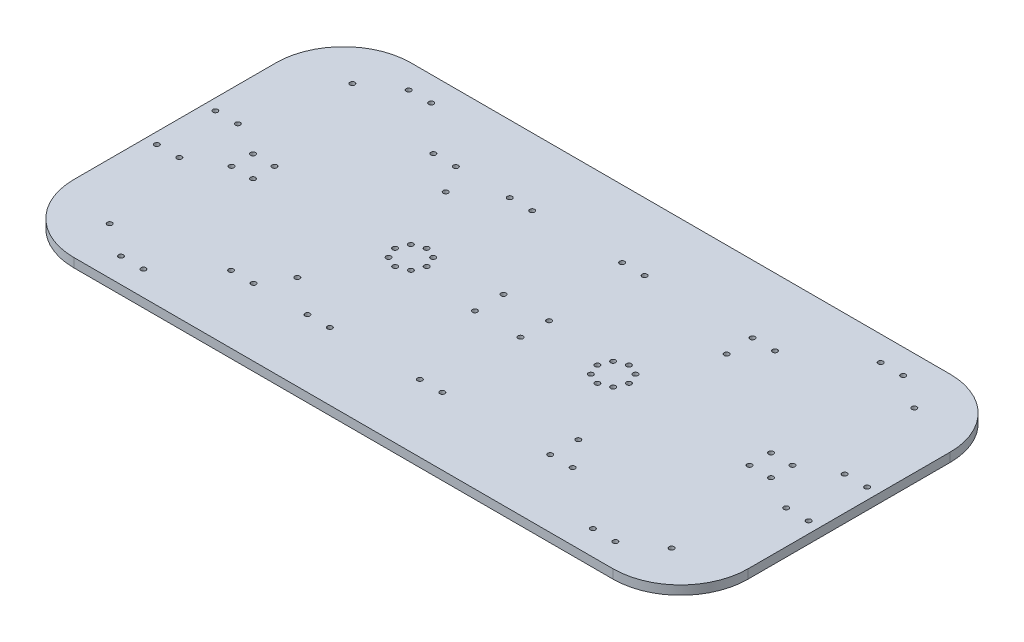
SolidWorks part; units mm, degrees
ref_plane "前视基准面" through (0, 0, 0) normal (0, 0, 1) x (1, 0, 0)
ref_plane "上视基准面" through (0, 0, 0) normal (0, 1, 0) x (1, 0, 0)
ref_plane "右视基准面" through (0, 0, 0) normal (1, 0, 0) x (0, 0, -1)
other "Configuration Table"
sketch "草图1" plane through (0, 0, 0) normal (0, 1, 0) x (1, 0, 0)
  line L1 (-150, 75) -> (150, 75)
  line L2 (-150, 75) -> (-150, -75)
  line L3 (-150, -75) -> (150, -75)
  line L4 (150, 75) -> (150, -75)
  dimension "D1" = 150
  dimension "D2" = 150
  dimension "D3" = 300
  dimension "D4" = 75
extrude "凸台-拉伸1" add sketch "草图1" along normal blind 4
fillet "圆角4" radius 30 1 edges at (-150, 2, 75) type face fillet first side face at (-150, 2, 0) second side face at (0, 2, 75)
fillet "圆角5" radius 30 1 edges at (-150, 2, -75) type face fillet first side face at (-150, 2, -15) second side face at (0, 2, -75)
fillet "圆角6" radius 30 1 edges at (150, 2, -75) type face fillet first side face at (15, 2, -75) second side face at (150, 2, 0)
fillet "圆角7" radius 30 1 edges at (150, 2, 75) type face fillet first side face at (150, 2, 15) second side face at (15, 2, 75)
sketch "草图2" plane through (0, 0, 0) normal (0, -1, 0) x (1, 0, 0)
  line L0 (0, 0) -> (-45, 0)
  line L1 (2.2, 0) -> (-2.2, 0) construction
  line L3 (0, -2.2) -> (0, 2.2) construction
  point P5 (-45, 7.02)
  dimension "D1" = 45
  dimension "D2" = 45
  dimension "D3" = 7.02
hole_wizard "Ø2.2 (2.2) 直径孔1" positions "草图3" profile "草图4" hole size "Ø2.2" standard "ANSI Metric" end condition up to next
sketch "草图3" plane through (0, 0, 0) normal (0, -1, 0) x (-1, 0, 0)
  point P0 (45, -7.02)
sketch "草图4" plane through (-45, 0, 7.02) normal (1, 0, 0) x (0, 0, -1)
  line L0 (0, 0) -> (0, 4)
  line L1 (0, 4) -> (1.1, 4)
  line L2 (1.1, 4) -> (1.1, 0)
  line L5 (1.1, 0) -> (0, 0)
  line L11 (0, -6.35) -> (0, 107.95) construction
  dimension "通孔孔直径" = 2.2
  dimension "通孔孔深度" = 4
ref_axis "基准轴1" through (-45, 0, 0) along (0, -1, 0)
pattern_circular "阵列(圆周)1" count 8 over 360 about axis through (-45, 0, 0) along (0, -1, 0) of "Ø2.2 (2.2) 直径孔1" reverse direction yes
mirror "镜向1" about plane through (0, 0, 0) normal (1, 0, 0) of "阵列(圆周)1", "Ø2.2 (2.2) 直径孔1"
sketch "草图5" plane through (0, 0, 0) normal (0, -1, 0) x (1, 0, 0)
  line L0 (-150, -45) -> (-150, 45) construction
  line L1 (2.2, 0) -> (-2.2, 0) construction
  point P0 (-120, 4.775)
  point P1 (-120, -4.78)
  point P6 (-110.45, -4.78)
  point P7 (-110.45, 4.775)
  dimension "D1" = 30
  dimension "D2" = 4.775
  dimension "D3" = 4.78
  dimension "D4" = 30
  dimension "D5" = 9.55
  dimension "D6" = 4.78
  dimension "D7" = 4.775
  dimension "D8" = 9.55
hole_wizard "Ø2.2 (2.2) 直径孔2" positions "草图6" profile "草图7" hole size "Ø2.2" standard "ANSI Metric" end condition up to next
sketch "草图6" plane through (0, 0, 0) normal (0, -1, 0) x (-1, 0, 0)
  point P0 (120, 4.78)
  point P3 (120, -4.775)
  point P6 (110.45, -4.775)
  point P9 (110.45, 4.78)
sketch "草图7" plane through (-120, 0, -4.78) normal (1, 0, 0) x (0, 0, -1)
  line L0 (0, 0) -> (0, 4)
  line L1 (0, 4) -> (1.1, 4)
  line L2 (1.1, 4) -> (1.1, 0)
  line L5 (1.1, 0) -> (0, 0)
  line L11 (0, -6.35) -> (0, 107.95) construction
  dimension "通孔孔直径" = 2.2
  dimension "通孔孔深度" = 4
mirror "镜向2" about plane through (0, 0, 0) normal (1, 0, 0) of "Ø2.2 (2.2) 直径孔2"
sketch "草图8" plane through (0, 4, 0) normal (0, 1, 0) x (1, 0, 0)
  line L0 (0, -2.2) -> (0, 2.2) construction
  line L1 (0, 0) -> (-45, 0) construction
  line L2 (-2.2, 0) -> (2.2, 0) construction
  point P0 (-30, 18)
  point P1 (-40, 18)
  point P2 (-40, -18)
  point P3 (-30, -18)
  dimension "D1" = 30
  dimension "D2" = 18
  dimension "D3" = 40
  dimension "D4" = 18
  dimension "D5" = 18
  dimension "D6" = 40
  dimension "D7" = 30
  dimension "D8" = 18
hole_wizard "Ø2.2 (2.2) 直径孔4" positions "草图13" profile "草图14" hole size "Ø2.2" standard "ANSI Metric" end condition up to next
sketch "草图13" plane through (0, 4, 0) normal (0, 1, 0) x (1, 0, 0)
  line L0 (-120, -75) -> (120, -75) construction
  line L1 (0, -2.2) -> (0, 2.2) construction
  point P0 (100, -64)
  point P2 (110, -64)
  point P4 (-100, -64)
  point P6 (-110, -64)
  dimension "D1" = 11
  dimension "D2" = 11
  dimension "D3" = 11
  dimension "D4" = 11
  dimension "D5" = 110
  dimension "D6" = 100
  dimension "D7" = 110
  dimension "D8" = 100
sketch "草图14" plane through (100, 4, 64) normal (1, 0, 0) x (0, 0, 1)
  line L0 (0, 0) -> (0, 4)
  line L1 (0, 4) -> (1.1, 4)
  line L2 (1.1, 4) -> (1.1, 0)
  line L5 (1.1, 0) -> (0, 0)
  line L11 (0, -6.35) -> (0, 107.95) construction
  dimension "通孔孔直径" = 2.2
  dimension "通孔孔深度" = 4
mirror "镜向4" about plane through (0, 0, 0) normal (0, 0, 1) of "Ø2.2 (2.2) 直径孔4"
hole_wizard "Ø2.2 (2.2) Diameter Hole1" positions "草图15" profile "草图16" hole size "Ø2.2" standard "ANSI Metric" end condition up to next
sketch "草图15" plane through (0, 4, 0) normal (0, 1, 0) x (1, 0, 0)
  line L0 (0, -2.2) -> (0, 2.2) construction
  line L1 (-2.2, 0) -> (2.2, 0) construction
  point P0 (-125, 54)
  dimension "D1" = 125
  dimension "D2" = 54
sketch "草图16" plane through (-125, 4, -54) normal (1, 0, 0) x (0, 0, 1)
  line L0 (0, 0) -> (0, 4)
  line L1 (0, 4) -> (1.1, 4)
  line L2 (1.1, 4) -> (1.1, 0)
  line L5 (1.1, 0) -> (0, 0)
  line L11 (0, -6.35) -> (0, 107.95) construction
  dimension "通孔孔直径" = 2.2
  dimension "通孔孔深度" = 4
mirror "镜向5" about plane through (0, 0, 0) normal (1, 0, 0) of "Ø2.2 (2.2) Diameter Hole1" second plane through (0, 0, 0) second plane normal (0, 0, 1)
hole_wizard "Ø2.2 (2.2) 直径孔6" positions "草图17" profile "草图18" hole size "Ø2.2" standard "ANSI Metric" end condition up to next
sketch "草图17" plane through (0, 4, 0) normal (0, 1, 0) x (1, 0, 0)
  line L0 (0, -2.2) -> (0, 2.2) construction
  line L1 (-2.2, 0) -> (2.2, 0) construction
  point P0 (-62.5, 33)
  point P13 (-62.5, -33)
  point P14 (62.5, -33)
  point P15 (62.5, 33)
  dimension "D1" = 62.5
  dimension "D2" = 33
sketch "草图18" plane through (-62.5, 4, -33) normal (1, 0, 0) x (0, 0, 1)
  line L0 (0, 0) -> (0, 4)
  line L1 (0, 4) -> (1.1, 4)
  line L2 (1.1, 4) -> (1.1, 0)
  line L5 (1.1, 0) -> (0, 0)
  line L11 (0, -6.35) -> (0, 107.95) construction
  dimension "通孔孔直径" = 2.2
  dimension "通孔孔深度" = 4
sketch "草图19" plane through (0, 4, 0) normal (0, 1, 0) x (1, 0, 0)
  line L0 (-150, 45) -> (-150, -45) construction
  point P0 (-145, 13)
  point P2 (-135, 13)
  dimension "D1" = 5
  dimension "D2" = 10
  dimension "D3" = 13
  dimension "D4" = 13
hole_wizard "Ø2.2 (2.2) Diameter Hole2" positions "草图19" profile "草图20" hole size "Ø2.2" standard "ANSI Metric" end condition up to next
sketch "草图20" plane through (-145, 4, -13) normal (1, 0, 0) x (0, 0, 1)
  line L0 (0, 0) -> (0, 4)
  line L1 (0, 4) -> (1.1, 4)
  line L2 (1.1, 4) -> (1.1, 0)
  line L5 (1.1, 0) -> (0, 0)
  line L11 (0, -6.35) -> (0, 107.95) construction
  dimension "Thru Hole Dia." = 2.2
  dimension "Thru Hole Depth" = 4
mirror "镜向6" about plane through (0, 0, 0) normal (1, 0, 0) of "Ø2.2 (2.2) Diameter Hole2" second plane through (0, 0, 0) second plane normal (0, 0, 1)
sketch "草图21" plane through (0, 4, 0) normal (0, 1, 0) x (1, 0, 0)
  line L0 (-2.2, 0) -> (2.2, 0) construction
  line L1 (-150, 45) -> (-150, -45) construction
  line L2 (150, -45) -> (150, 45) construction
  point P0 (-80, 45)
  point P2 (-70, 45)
  point P4 (-46, 45)
  point P6 (-36, 45)
  point P8 (4, 45)
  point P10 (14, 45)
  point P23 (62, 45)
  point P25 (72, 45)
  dimension "D1" = 45
  dimension "D2" = 45
  dimension "D3" = 45
  dimension "D4" = 45
  dimension "D5" = 10
  dimension "D6" = 10
  dimension "D7" = 70
  dimension "D8" = 34
  dimension "D9" = 45
  dimension "D10" = 45
  dimension "D11" = 10
  dimension "D12" = 45
  dimension "D13" = 45
  dimension "D14" = 58
  dimension "D15" = 78
  dimension "D16" = 10
hole_wizard "Ø2.2 (2.2) Diameter Hole3" positions "草图21" profile "草图22" hole size "Ø2.2" standard "ANSI Metric" end condition up to next
sketch "草图22" plane through (-80, 4, -45) normal (1, 0, 0) x (0, 0, 1)
  line L0 (0, 0) -> (0, 4)
  line L1 (0, 4) -> (1.1, 4)
  line L2 (1.1, 4) -> (1.1, 0)
  line L5 (1.1, 0) -> (0, 0)
  line L11 (0, -6.35) -> (0, 107.95) construction
  dimension "Thru Hole Dia." = 2.2
  dimension "Thru Hole Depth" = 4
mirror "镜向7" about plane through (0, 0, 0) normal (0, 0, 1) of "Ø2.2 (2.2) Diameter Hole3"
sketch "草图23" plane through (0, 0, 0) normal (0, -1, 0) x (1, 0, 0)
  line L0 (0, -2.2) -> (0, 2.2) construction
  line L1 (2.2, 0) -> (-2.2, 0) construction
  point P0 (-10.16, 6.35)
  dimension "D1" = 10.16
  dimension "D2" = 6.35
hole_wizard "Ø2.2 (2.2) Diameter Hole4" positions "草图23" profile "草图24" hole size "Ø2.2" standard "ANSI Metric" end condition up to next
sketch "草图24" plane through (-10.16, 0, 6.35) normal (1, 0, 0) x (0, 0, -1)
  line L0 (0, 0) -> (0, 4)
  line L1 (0, 4) -> (1.1, 4)
  line L2 (1.1, 4) -> (1.1, 0)
  line L5 (1.1, 0) -> (0, 0)
  line L11 (0, -6.35) -> (0, 107.95) construction
  dimension "Thru Hole Dia." = 2.2
  dimension "Thru Hole Depth" = 4
mirror "镜向8" about plane through (0, 0, 0) normal (0, 0, 1) of "Ø2.2 (2.2) Diameter Hole4" second plane through (0, 0, 0) second plane normal (1, 0, 0)
